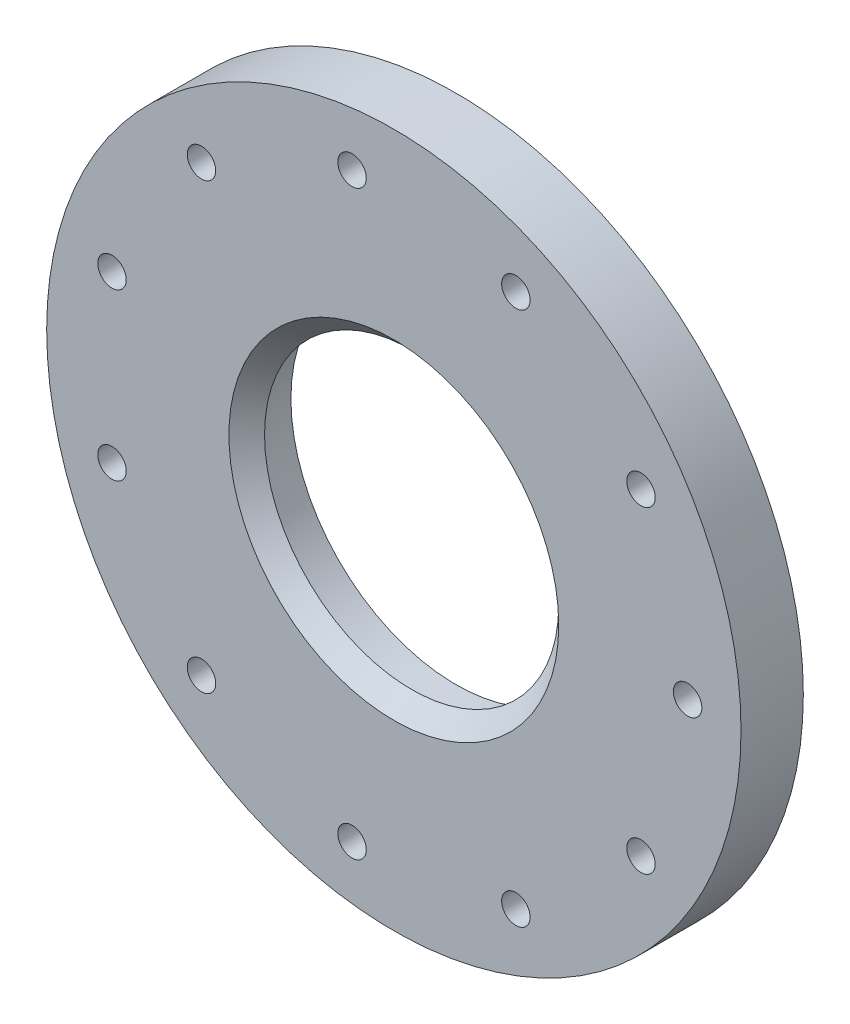
SolidWorks part; units mm, degrees
ref_plane "Front Plane" through (0, 0, 0) normal (0, 0, 1) x (1, 0, 0)
ref_plane "Top Plane" through (0, 0, 0) normal (0, 1, 0) x (1, 0, 0)
ref_plane "Right Plane" through (0, 0, 0) normal (1, 0, 0) x (0, 0, -1)
ref_plane "Plane1" through (0, 0, 15) normal (0, 0, 1) x (1, 0, 0)
sketch "Sketch1" plane through (0, 0, 15) normal (0, 0, 1) x (1, 0, 0)
  circle A0 centre (0, 0) radius 39
  circle A1 centre (0, 0) radius 33 construction
  circle A2 centre (33, 0) radius 2.5
  circle A3 centre (27.7614, -17.8411) radius 2.5
  circle A4 centre (13.7087, -30.0179) radius 2.5
  circle A5 centre (-4.6964, -32.6641) radius 2.5
  circle A6 centre (-21.6104, -24.9397) radius 2.5
  circle A7 centre (-31.6633, -9.2972) radius 2.5
  circle A8 centre (-31.6633, 9.2972) radius 2.5
  circle A9 centre (-21.6104, 24.9397) radius 2.5
  circle A10 centre (-4.6964, 32.6641) radius 2.5
  circle A11 centre (13.7087, 30.0179) radius 2.5
  circle A12 centre (27.7614, 17.8411) radius 2.5
  circle A13 centre (0, 0) radius 16.025
  point P28 (0, 0)
extrude "Boss-Extrude1" add sketch "Sketch1" along normal blind 7
sketch "Sketch2" plane through (0, 0, 15) normal (0, 0, -1) x (-1, 0, 0)
  circle A0 centre (0, 0) radius 18.5625
  dimension "D1" = 37.125
extrude "Cut-Extrude1" cut sketch "Sketch2" against normal blind 5
sketch "Sketch3" plane through (0, 0, 22) normal (0, 0, 1) x (1, 0, 0)
  circle A0 centre (-4.6964, 32.6641) radius 1.6
  circle A1 centre (-4.6964, 32.6641) radius 2.5
  circle A2 centre (13.7087, 30.0179) radius 2.5
  circle A3 centre (13.7087, 30.0179) radius 1.6
  circle A4 centre (27.7614, 17.8411) radius 2.5
  circle A5 centre (27.7614, 17.8411) radius 1.6
  circle A6 centre (33, 0) radius 2.5
  circle A7 centre (33, 0) radius 1.6
  circle A8 centre (27.7614, -17.8411) radius 2.5
  circle A9 centre (27.7614, -17.8411) radius 1.6
  circle A10 centre (13.7087, -30.0179) radius 2.5
  circle A11 centre (13.7087, -30.0179) radius 1.6
  circle A12 centre (-4.6964, -32.6641) radius 2.5
  circle A13 centre (-4.6964, -32.6641) radius 1.6
  circle A14 centre (-21.6104, -24.9397) radius 2.5
  circle A15 centre (-21.6104, -24.9397) radius 1.6
  circle A16 centre (-31.6633, -9.2972) radius 2.5
  circle A17 centre (-31.6633, -9.2972) radius 1.6
  circle A18 centre (-31.6633, 9.2972) radius 2.5
  circle A19 centre (-31.6633, 9.2972) radius 1.6
  circle A20 centre (-21.6104, 24.9397) radius 2.5
  circle A21 centre (-21.6104, 24.9397) radius 1.6
  point P5 (0, 0)
  point P6 (1.2547, -3.0229)
  point P36 (0, 0)
  point P37 (0, 0)
  dimension "D1" = 5
  dimension "D2" = 3.2
  dimension "D3" = 11
extrude "Boss-Extrude2" add sketch "Sketch3" against normal blind 4
chamfer "Chamfer1" distance 2.5 angle 45 1 edges at (16.025, 0, 22)
